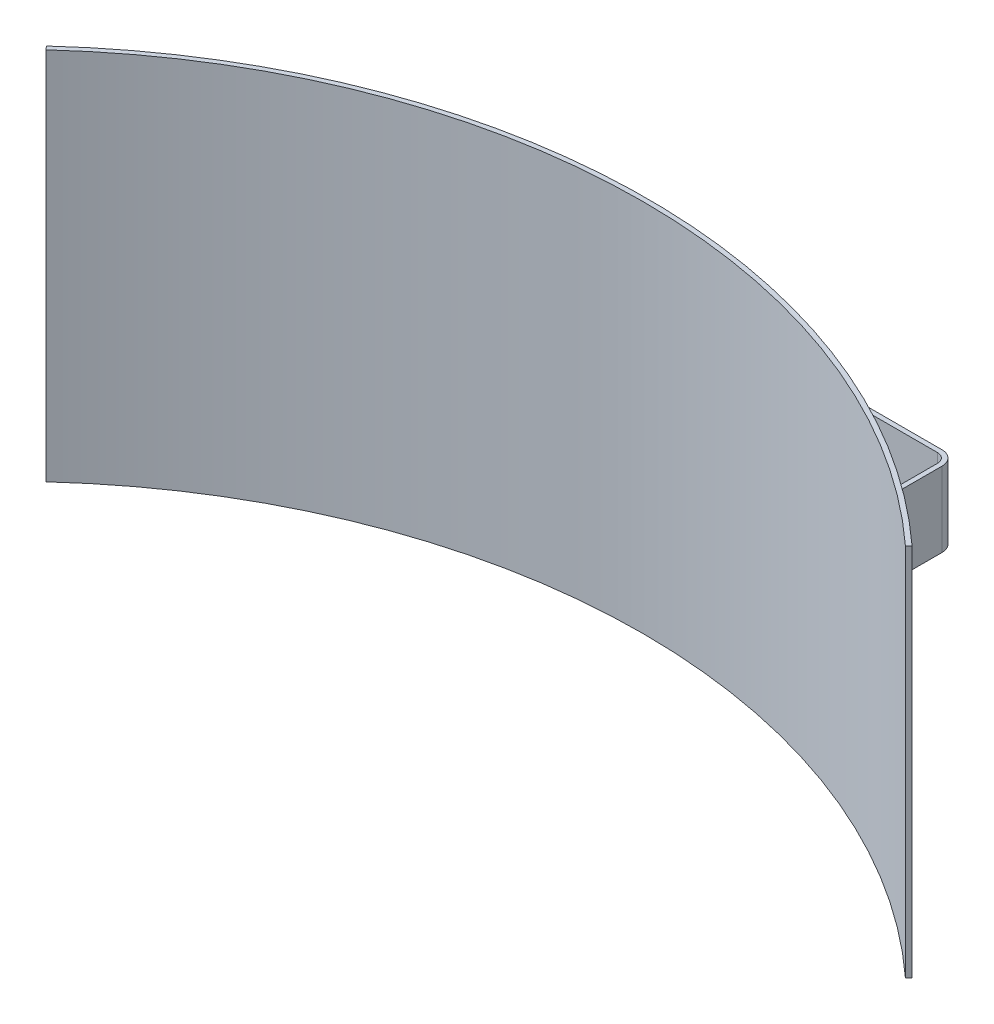
SolidWorks part; units mm, degrees
ref_plane "Front Plane" through (0, 0, 0) normal (0, 0, 1) x (1, 0, 0)
ref_plane "Top Plane" through (0, 0, 0) normal (0, 1, 0) x (1, 0, 0)
ref_plane "Right Plane" through (0, 0, 0) normal (1, 0, 0) x (0, 0, -1)
sketch "Sketch1" plane through (0, 0, 0) normal (0, 1, 0) x (1, 0, 0)
  line L0 (0, 0) -> (146.9324, 160.3486) construction
  line L1 (0, 0) -> (-146.9324, 160.3486) construction
  line L3 (0, 0) -> (0, 215.9) construction
  line L4 (146.9324, 160.3486) -> (145.8599, 159.1782)
  line L5 (-146.9324, 160.3486) -> (-145.8599, 159.1782)
  circle A0 centre (0, 0) radius 215.9 construction
  circle A1 centre (0, 0) radius 217.4875 construction
  arc A2 (145.8599, 159.1782) -> (-145.8599, 159.1782) centre (0, 0) ccw
  arc A3 (146.9324, 160.3486) -> (-146.9324, 160.3486) centre (0, 0) ccw
  dimension "D1" = 431.8
  dimension "D3" = 85
  dimension "D4" = 42.5
  dimension "D2" = 1.5875
extrude "Boss-Extrude1" add sketch "Sketch1" along normal mid plane 127
sketch "Sketch2" plane through (0, 0, 0) normal (0, 1, 0) x (1, 0, 0)
  line L0 (0, 217.4875) -> (0, 260.8018) construction
  line L1 (73.025, 242.8875) -> (-73.025, 242.8875)
  line L2 (-76.2, 239.7125) -> (-76.2, 205.8921)
  line L3 (76.2, 239.7125) -> (76.2, 205.8921)
  line L4 (77.7875, 239.7125) -> (77.7875, 205.8921)
  line L5 (73.025, 244.475) -> (-73.025, 244.475)
  line L6 (-77.7875, 239.7125) -> (-77.7875, 205.8921)
  line L7 (102.3416, 193.7009) -> (101.6, 192.2973)
  line L8 (-102.3416, 193.7009) -> (-101.6, 192.2973)
  arc A0 (146.9324, 160.3486) -> (-146.9324, 160.3486) centre (0, 0) ccw construction
  arc A1 (-78.2329, 202.9296) -> (-101.6, 192.2973) centre (0, 0) ccw
  arc A2 (-76.2, 205.8921) -> (-78.2329, 202.9296) centre (-79.375, 205.8921) cw
  arc A3 (-76.2, 239.7125) -> (-73.025, 242.8875) centre (-73.025, 239.7125) cw
  arc A4 (78.2329, 202.9296) -> (101.6, 192.2973) centre (0, 0) cw
  arc A5 (76.2, 205.8921) -> (78.2329, 202.9296) centre (79.375, 205.8921) ccw
  arc A6 (76.2, 239.7125) -> (73.025, 242.8875) centre (73.025, 239.7125) ccw
  arc A7 (78.804, 204.4108) -> (102.3416, 193.7009) centre (0, 0) cw
  arc A8 (77.7875, 205.8921) -> (78.804, 204.4108) centre (79.375, 205.8921) ccw
  arc A9 (77.7875, 239.7125) -> (73.025, 244.475) centre (73.025, 239.7125) ccw
  arc A10 (-77.7875, 239.7125) -> (-73.025, 244.475) centre (-73.025, 239.7125) cw
  arc A11 (-77.7875, 205.8921) -> (-78.804, 204.4108) centre (-79.375, 205.8921) cw
  arc A12 (-78.804, 204.4108) -> (-102.3416, 193.7009) centre (0, 0) ccw
  point P13 (-76.2, 203.7017)
  point P16 (-76.2, 242.8875)
  point P24 (76.2, 242.8875)
  point P25 (0, 242.8875)
  dimension "D3" = 25.4
  dimension "D4" = 3.175
  dimension "D1" = 76.2
  dimension "D2" = 25.4
  dimension "D5" = 1.5875
extrude "Boss-Extrude2" add sketch "Sketch2" along normal mid plane 25.4
equation "\"D4@Sketch1\"=\"D3@Sketch1\"/2"
